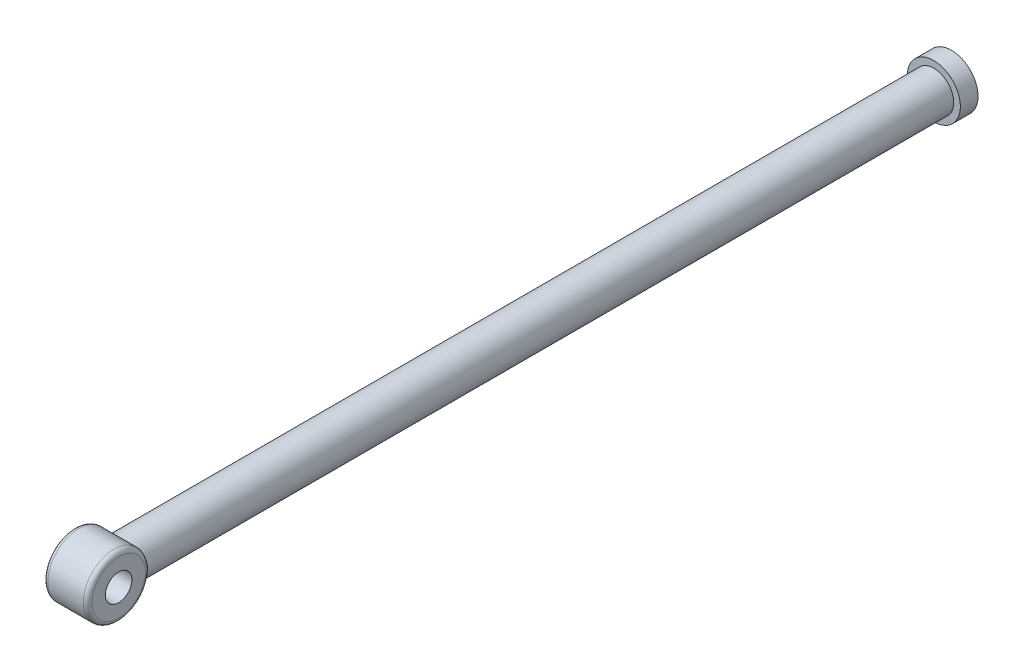
SolidWorks part; units mm, degrees
material "Cast Carbon Steel"
ref_plane "Front" through (0, 0, 0) normal (0, 0, 1) x (1, 0, 0)
ref_plane "Top" through (0, 0, 0) normal (0, 1, 0) x (1, 0, 0)
ref_plane "Right" through (0, 0, 0) normal (1, 0, 0) x (0, 0, -1)
sketch "Sketch2" plane through (0, 0, 0) normal (0, 0, 1) x (1, 0, 0)
  circle A0 centre (0, 0) radius 22.5
  dimension "D1" = 45
extrude "Boss-Extrude1" add sketch "Sketch2" along normal blind 946
sketch "Sketch3" plane through (0, 0, 0) normal (0, 0, -1) x (-1, 0, 0)
  circle A0 centre (0, 0) radius 30
  dimension "D1" = 60
extrude "Boss-Extrude2" add sketch "Sketch3" along normal blind 20
sketch "Sketch4" plane through (0, 0, 0) normal (1, 0, 0) x (0, 0, -1)
  line L0 (-946, 22.5) -> (-946, -22.5) construction
  circle A0 centre (-946, 0) radius 35
  dimension "D1" = 70
extrude "Boss-Extrude3" add sketch "Sketch4" along normal mid plane 50
sketch "Sketch5" plane through (25, 0, 0) normal (1, 0, 0) x (0, 0, -1)
  circle A0 centre (-946, 0) radius 15
  dimension "D1" = 30
extrude "Cut-Extrude1" cut sketch "Sketch5" against normal through all
fillet "Fillet1" radius 5 2 edges at (-25, 0, 911) (25, 0, 911)
